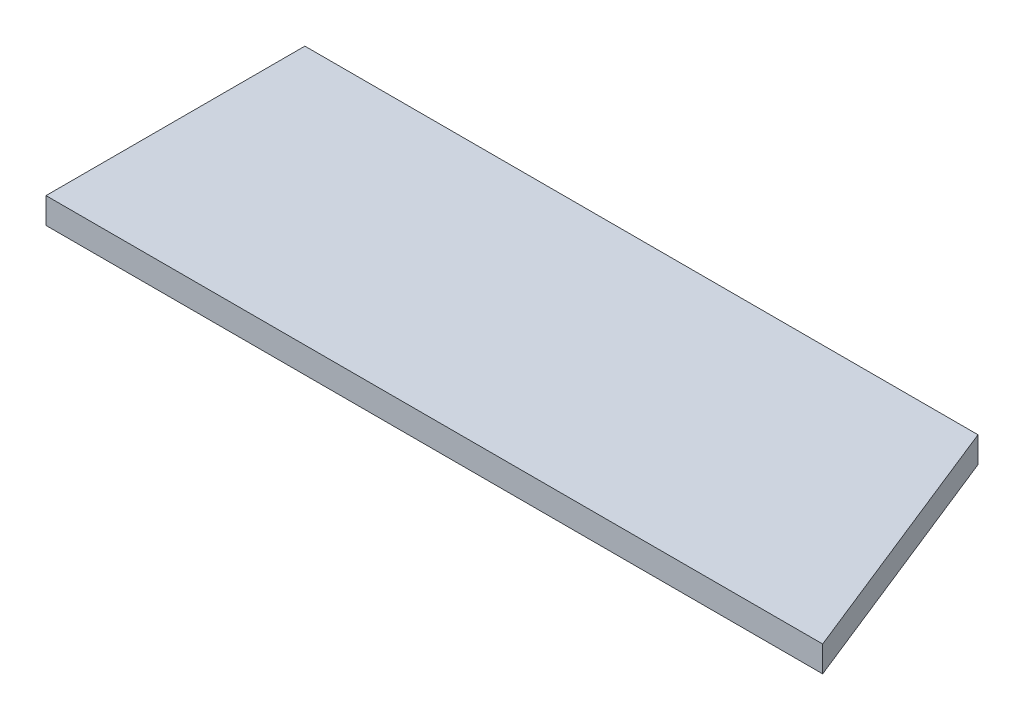
SolidWorks part; units mm, degrees
ref_plane "Спереди" through (0, 0, 0) normal (0, 0, 1) x (1, 0, 0)
ref_plane "Сверху" through (0, 0, 0) normal (0, 1, 0) x (1, 0, 0)
ref_plane "Справа" through (0, 0, 0) normal (1, 0, 0) x (0, 0, -1)
sketch "Эскиз1" plane through (0, 0, 0) normal (0, 1, 0) x (1, 0, 0)
  line L0 (0, 0) -> (150, 0)
  line L1 (150, 0) -> (130, 50)
  line L2 (130, 50) -> (0, 50)
  line L3 (0, 50) -> (0, 0)
  point P3 (0, 0)
extrude "Бобышка-Вытянуть1" add sketch "Эскиз1" along normal blind 5
